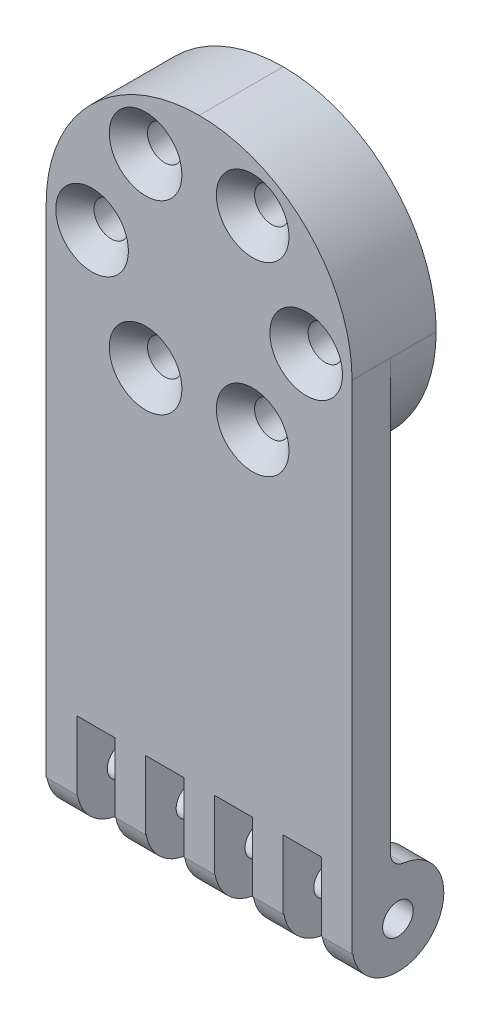
SolidWorks part; units mm, degrees
other "Markup1"
sketch "Sketch13" plane through (20, -53, 11) normal (0.0614, -0.6805, 0.7302) x (0.9699, -0.1321, -0.2046)
ref_plane "Front Plane" through (0, 0, 0) normal (0, 0, 1) x (1, 0, 0)
ref_plane "Top Plane" through (0, 0, 0) normal (0, 1, 0) x (1, 0, 0)
ref_plane "Right Plane" through (0, 0, 0) normal (1, 0, 0) x (0, 0, -1)
sketch "Sketch7" plane through (0, 0, 0) normal (0, 0, 1) x (1, 0, 0)
  line L1 (-20, 20) -> (20, 20)
  line L2 (-20, 20) -> (-20, -20)
  line L3 (-20, -20) -> (20, -20)
  line L4 (20, 20) -> (20, -20)
  line L5 (-20, 20) -> (20, -20) construction
  line L6 (-20, -20) -> (20, 20) construction
  point P0 (0, 0)
extrude "Boss-Extrude1" add sketch "Sketch7" along normal blind 11
sketch "Sketch8" plane through (0, -20, 0) normal (0, -1, 0) x (1, 0, 0)
  line L0 (20, 11) -> (20, 0) construction
  line L1 (-20, 11) -> (20, 11)
  line L2 (-20, 11) -> (-20, 6)
  line L3 (-20, 6) -> (20, 6)
  line L4 (20, 11) -> (20, 6)
  line L5 (0, 6) -> (0, 11) construction
  line L6 (-20, 8.5) -> (20, 8.5) construction
  line L7 (-20, 0) -> (20, 0) construction
  point P764 (0, 8.5)
  dimension "D1" = 6
extrude "Boss-Extrude2" add sketch "Sketch8" along normal blind 36
sketch "Sketch10" plane through (0, 0, 11) normal (0, 0, 1) x (1, 0, 0)
  circle A0 centre (-7.0001, 12.1244) radius 2.25
  circle A1 centre (6.9999, 12.1244) radius 2.25
  circle A2 centre (13.9999, 0.0001) radius 2.25
  circle A3 centre (6.9999, -12.1243) radius 2.25
  circle A4 centre (-7.0001, -12.1243) radius 2.25
  circle A5 centre (-14.0001, 0.0001) radius 2.25
  point P0 (0, 0)
  point P1 (0.0025, 0.0011)
  dimension "D4" = 4.5
extrude "Cut-Extrude1" cut sketch "Sketch10" against normal blind 25
fillet "Fillet1" radius 20 4 edges at (20, -20, 3) (20, 20, 5.5) (-20, 20, 5.5) (-20, -20, 3)
sketch "Sketch11" plane through (0, -56, 0) normal (0, -1, 0) x (1, 0, 0)
  line L0 (-20, 6) -> (20, 6) construction
  line L1 (-20, 11) -> (-16, 11)
  line L2 (-20, 11) -> (-20, 6)
  line L3 (-20, 6) -> (-16, 6)
  line L4 (-16, 11) -> (-16, 6)
  line L5 (-18, 6) -> (-18, 11) construction
  line L6 (-20, 8.5) -> (-16, 8.5) construction
  point P368 (-18, 8.5)
extrude "Boss-Extrude3" add sketch "Sketch11" along normal blind 9 contours L1 L4 L3 L2
ref_plane "Plane1" through (-16, 0, 0) normal (1, 0, 0) x (0, 0, -1)
sketch "Sketch14" plane through (-16, 0, 0) normal (1, 0, 0) x (0, 0, -1)
  line L0 (-11, -65) -> (-6, -65) construction
  line L2 (-11, 0) -> (-11, -65) construction
  circle A0 centre (-5, -64) radius 6
  dimension "D3" = 12
  dimension "D1" = 1
extrude "Boss-Extrude4" add sketch "Sketch14" against normal up to vertex (4 mm away) up to point (-20, -65, 11)
pattern_linear "LPattern1" count 5 spacing 9 along (1, 0, 0) of "Boss-Extrude4", "Boss-Extrude3"
sketch "Sketch15" plane through (-20, 0, 0) normal (-1, 0, 0) x (0, 0, 1)
  circle A0 centre (5, -64) radius 2
extrude "Cut-Extrude2" cut sketch "Sketch15" against normal through all
chamfer "Chamfer1" distance 2.5 angle 45 6 edges at (-4.7501, 12.1244, 11) (-11.7501, 0.0001, 11) (-4.7501, -12.1243, 11) (9.2499, 12.1244, 11) (16.2499, 0.0001, 11) (9.2499, -12.1243, 11)
fillet "Fillet2" radius 2 5 edges at (18, -58.0839, 6) (9, -58.0839, 6) (0, -58.0839, 6) (-9, -58.0839, 6) (-18, -58.0839, 6)
